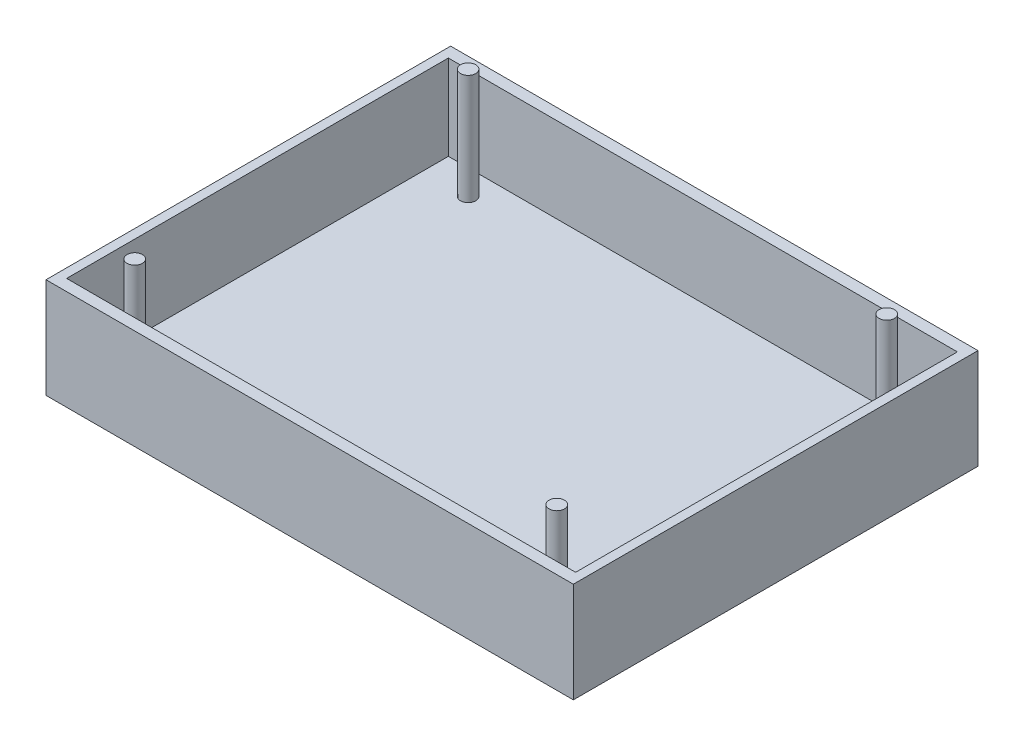
SolidWorks part; units mm, degrees
ref_plane "Front Plane" through (0, 0, 0) normal (0, 0, 1) x (1, 0, 0)
ref_plane "Top Plane" through (0, 0, 0) normal (0, 1, 0) x (1, 0, 0)
ref_plane "Right Plane" through (0, 0, 0) normal (1, 0, 0) x (0, 0, -1)
sketch "Sketch1" plane through (0, 0, 0) normal (0, 1, 0) x (1, 0, 0)
  line L1 (-50.8, -38.1) -> (50.8, -38.1)
  line L2 (-50.8, -38.1) -> (-50.8, 38.1)
  line L3 (-50.8, 38.1) -> (50.8, 38.1)
  line L4 (50.8, -38.1) -> (50.8, 38.1)
  line L5 (-50.8, -38.1) -> (50.8, 38.1) construction
  line L6 (-50.8, 38.1) -> (50.8, -38.1) construction
  line L7 (-41.91, -33.147) -> (41.91, -33.147) construction
  line L8 (-41.91, -33.147) -> (-41.91, 33.147) construction
  line L9 (-41.91, 33.147) -> (41.91, 33.147) construction
  line L10 (41.91, -33.147) -> (41.91, 33.147) construction
  line L11 (-41.91, -33.147) -> (41.91, 33.147) construction
  line L12 (-41.91, 33.147) -> (41.91, -33.147) construction
  line L13 (-52.6322, -40.3845) -> (52.6322, -40.3845)
  line L14 (-52.6322, -40.3845) -> (-52.6322, 40.3845)
  line L15 (-52.6322, 40.3845) -> (52.6322, 40.3845)
  line L16 (52.6322, -40.3845) -> (52.6322, 40.3845)
  line L17 (-52.6322, -40.3845) -> (52.6322, 40.3845) construction
  line L18 (-52.6322, 40.3845) -> (52.6322, -40.3845) construction
  circle A0 centre (-41.91, 33.147) radius 1.524
  circle A1 centre (42.2051, 32.6055) radius 1.524
  circle A2 centre (42.2051, -33.2675) radius 1.524
  circle A3 centre (-42.3706, -32.9365) radius 1.524
  point P0 (0, 0)
  point P6 (0, 0)
  point P21 (0, 0)
extrude "Boss-Extrude1" add sketch "Sketch1" along normal blind 3 contours L1 L4 L3 L2 A3 A2 A1 A0 region at (-0.0001, 0, -0.0004)
extrude "Boss-Extrude2" add sketch "Sketch1<3>" along normal blind 25 contours A3 | A0 | A1 | A2
sketch "Sketch1<3>" plane through (0, 0, 0) normal (0, 1, 0) x (1, 0, 0) same geometry as "Sketch1"
extrude "Boss-Extrude3" add sketch "Sketch1<4>" along normal blind 20 contours L13 L16 L15 L14 L4 L1 L2 L3 region at (-51.3054, 0, 0)
sketch "Sketch1<4>" plane through (0, 0, 0) normal (0, 1, 0) x (1, 0, 0) same geometry as "Sketch1"
